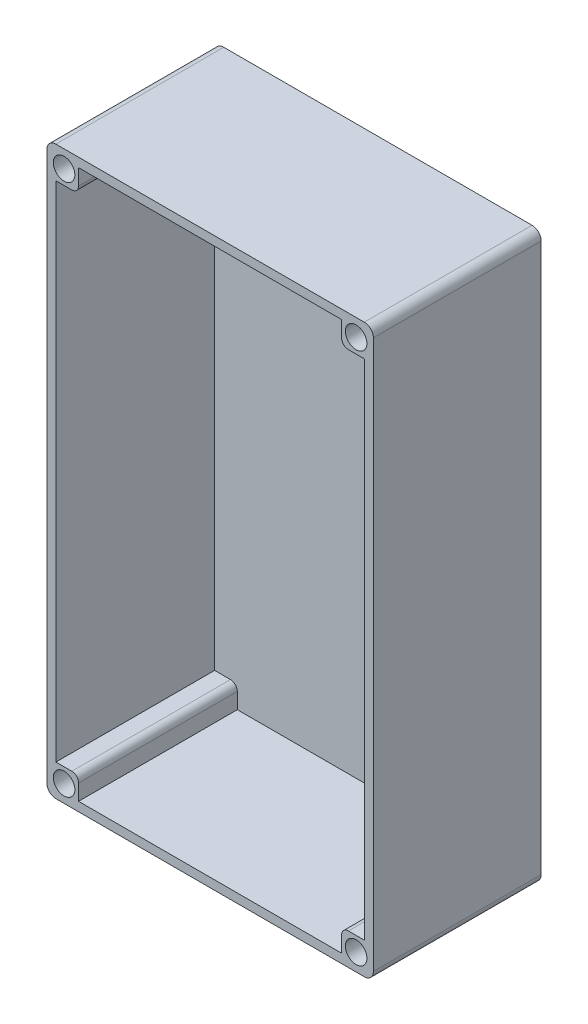
SolidWorks part; units mm, degrees
ref_plane "Front Plane" through (0, 0, 0) normal (0, 0, 1) x (1, 0, 0)
ref_plane "Top Plane" through (0, 0, 0) normal (0, 1, 0) x (1, 0, 0)
ref_plane "Right Plane" through (0, 0, 0) normal (1, 0, 0) x (0, 0, -1)
sketch "Sketch1" plane through (0, 0, 0) normal (0, 0, 1) x (1, 0, 0)
  line L5 (-36, 50) -> (36, 50)
  line L6 (-36, 50) -> (-36, -75)
  line L7 (-36, -75) -> (36, -75)
  line L8 (36, 50) -> (36, -75)
  dimension "D1" = 72
  dimension "D2" = 36
  dimension "D3" = 125
  dimension "D4" = 75
extrude "Boss-Extrude1" add sketch "Sketch1" along normal blind 2
sketch "Sketch2" plane through (0, 0, 2) normal (0, 0, 1) x (1, 0, 0)
  circle A0 centre (-22.86, 38.1) radius 2.3812
  circle A1 centre (-22.86, 20.32) radius 2.3813
  circle A2 centre (22.86, 20.32) radius 2.3812
  circle A3 centre (22.86, 38.1) radius 2.3812
  dimension "D1" = 4.7625
  dimension "D2" = 4.7625
  dimension "D3" = 4.7625
  dimension "D4" = 4.7625
  dimension "D5" = 45.72
  dimension "D6" = 45.72
  dimension "D7" = 17.78
  dimension "D8" = 17.78
  dimension "D9" = 22.86
  dimension "D10" = 20.32
  dimension "D11" = 0
extrude "Boss-Extrude2" [suppressed] add sketch "Sketch2" along normal blind 3.175
sketch "Sketch3" [suppressed] plane through (0, 0, 2) normal (0, 0, 1) x (1, 0, 0)
  line L1 (-25.4, 41.275) -> (25.4, 41.275)
  line L2 (-25.4, 41.275) -> (-25.4, 18.415)
  line L3 (-25.4, 18.415) -> (25.4, 18.415)
  line L4 (25.4, 41.275) -> (25.4, 18.415)
  dimension "D1" = 22.86
  dimension "D2" = 1.905
  dimension "D3" = 2.54
  dimension "D4" = 50.8
fillet "Fillet1" [suppressed] radius 2
sketch "Sketch4" [suppressed] plane through (0, 0, 5.175) normal (0, 0, 1) x (1, 0, 0)
  circle A0 centre (-22.86, 38.1) radius 1.0795
  circle A1 centre (22.86, 38.1) radius 1.0795
  circle A2 centre (22.86, 20.32) radius 1.0795
  circle A3 centre (-22.86, 20.32) radius 1.0795
  dimension "D1" = 2.159
  dimension "D2" = 2.159
  dimension "D3" = 2.159
  dimension "D4" = 2.159
extrude "Cut-Extrude1" [suppressed] cut sketch "Sketch4" against normal through all
sketch "Sketch5" plane through (0, 0, 2) normal (0, 0, 1) x (1, 0, 0)
  line L0 (36, -75) -> (36, 50) construction
  line L1 (-36, 50) -> (36, 50)
  line L2 (-36, 50) -> (-36, 48)
  line L3 (-36, 48) -> (36, 48)
  line L4 (36, 50) -> (36, 48)
  dimension "D1" = 2
extrude "Boss-Extrude3" add sketch "Sketch5" along normal blind 35
sketch "Sketch6" plane through (0, 0, 2) normal (0, 0, 1) x (1, 0, 0)
  line L0 (-36, -75) -> (36, -75) construction
  line L1 (-34, -75) -> (-36, -75)
  line L2 (-34, -75) -> (-34, 50)
  line L3 (-34, 50) -> (-36, 50)
  line L4 (-36, -75) -> (-36, 50)
  dimension "D1" = 2
extrude "Boss-Extrude4" add sketch "Sketch6" along normal blind 35
mirror "Mirror1" [suppressed] about plane through (0, 0, 0) normal (0, 1, 0)
mirror "Mirror2" about plane through (0, 0, 0) normal (1, 0, 0) of "Boss-Extrude4"
mirror "Mirror3" [suppressed] about plane through (0, 0, 0) normal (0, 1, 0)
sketch "Sketch7" plane through (0, 0, 2) normal (0, 0, 1) x (1, 0, 0)
  line L1 (-29, 43) -> (-34, 43)
  line L2 (-29, 43) -> (-29, 48)
  line L3 (-29, 48) -> (-34, 48)
  line L4 (-34, 43) -> (-34, 48)
extrude "Boss-Extrude5" add sketch "Sketch7" along normal up to surface (35 mm away) up to face at (0, -13, 37)
fillet "Fillet2" radius 1.5 1 edges at (-29, 43, 19.5)
sketch "Sketch8" plane through (0, 0, 37) normal (0, 0, 1) x (1, 0, 0)
  line L0 (36, 50) -> (-36, 50) construction
  line L1 (-36, 50) -> (-36, -75) construction
  circle A0 centre (-32.2, 46.2) radius 2.375
  dimension "D1" = 4.75
  dimension "D3" = 3.8
extrude "Cut-Extrude2" cut sketch "Sketch8" against normal through all
mirror "Mirror4" about plane through (0, 0, 0) normal (1, 0, 0) of "Cut-Extrude2", "Boss-Extrude5", "Fillet2"
mirror "Mirror5" [suppressed] about plane through (0, 0, 0) normal (0, 1, 0)
fillet "Fillet3" radius 2 4 edges at (-36, 50, 18.5) (36, 50, 18.5) (-36, -75, 18.5) (36, -75, 18.5)
sketch "Sketch9" plane through (-36, 0, 0) normal (-1, 0, 0) x (0, 0, 1)
  line L0 (0, 48) -> (0, -73) construction
  line L1 (25.0475, 35) -> (14.9525, 35)
  line L2 (26, 34.0475) -> (26, 23.9525)
  line L3 (25.0475, 23) -> (14.9525, 23)
  line L4 (14, 34.0475) -> (14, 23.9525)
  line L5 (0, 50) -> (37, 50) construction
  arc A0 (26, 23.9525) -> (25.0475, 23) centre (25.0475, 23.9525) cw
  arc A1 (25.0475, 35) -> (26, 34.0475) centre (25.0475, 34.0475) cw
  arc A2 (14.9525, 35) -> (14, 34.0475) centre (14.9525, 34.0475) ccw
  arc A3 (14.9525, 23) -> (14, 23.9525) centre (14.9525, 23.9525) cw
  point P10 (26, 23)
  point P13 (26, 35)
  dimension "D5" = 0.9525
  dimension "D1" = 26
  dimension "D2" = 14
  dimension "D3" = 12
  dimension "D4" = 15
extrude "Cut-Extrude3" [suppressed] cut sketch "Sketch9" against normal up to next
sketch "Sketch10" [suppressed] plane through (0, 0, 0) normal (0, 0, -1) x (-1, 0, 0)
  circle A0 centre (22.86, 38.1) radius 1.905
  circle A1 centre (22.86, 20.32) radius 1.905
  dimension "D1" = 3.81
  dimension "D2" = 3.81
extrude "Cut-Extrude4" [suppressed] cut sketch "Sketch10" against normal blind 2.286
mirror "Mirror6" [suppressed] about plane through (0, 0, 0) normal (1, 0, 0)
mirror "Mirror7" [suppressed] about plane through (0, 0, 0) normal (0, 1, 0)
sketch "Sketch11" [suppressed] plane through (-28.575, 0, 0) normal (-1, 0, 0) x (0, 0, 1)
  line L0 (2.286, -20.32) -> (5.175, -20.32) construction
  line L1 (10.7295, -21.72) -> (27.2492, -21.72)
  line L2 (8.7295, -23.72) -> (8.7295, -34.72)
  line L3 (10.7295, -36.72) -> (27.2492, -36.72)
  line L4 (29.2492, -23.72) -> (29.2492, -34.72)
  arc A0 (8.7295, -34.72) -> (10.7295, -36.72) centre (10.7295, -34.72) ccw
  arc A1 (27.2492, -36.72) -> (29.2492, -34.72) centre (27.2492, -34.72) ccw
  arc A2 (27.2492, -21.72) -> (29.2492, -23.72) centre (27.2492, -23.72) cw
  arc A3 (10.7295, -21.72) -> (8.7295, -23.72) centre (10.7295, -23.72) ccw
  point P10 (29.2492, -36.72)
  point P13 (29.2492, -21.72)
  dimension "D3" = 2
  dimension "D1" = 15
  dimension "D2" = 1.4
extrude "Cut-Extrude5" [suppressed] cut sketch "Sketch11" against normal up to next
sketch "Sketch12" plane through (0, 0, 2) normal (0, 0, 1) x (1, 0, 0)
  line L0 (34, -75) -> (34, 43) construction
  line L1 (-34, -75) -> (34, -75)
  line L2 (-34, -75) -> (-34, -73)
  line L3 (-34, -73) -> (34, -73)
  line L4 (34, -75) -> (34, -73)
  dimension "D1" = 2
extrude "Boss-Extrude6" add sketch "Sketch12" along normal up to surface (35 mm away) up to face at (29.825, 46.2, 37)
sketch "Sketch13" plane through (0, 0, 37) normal (0, 0, 1) x (1, 0, 0)
  line L1 (-34, -73) -> (-29, -73)
  line L2 (-34, -73) -> (-34, -68)
  line L3 (-34, -68) -> (-29, -68)
  line L4 (-29, -73) -> (-29, -68)
  dimension "D1" = 5
  dimension "D2" = 5
extrude "Boss-Extrude9" add sketch "Sketch13" against normal up to surface (35 mm away) up to face at (0, 21.0379, 2)
sketch "Sketch14" plane through (0, 0, 37) normal (0, 0, 1) x (1, 0, 0)
  line L0 (-36, 48) -> (-36, -73) construction
  line L1 (-34, -75) -> (34, -75) construction
  circle A0 centre (-32.2, -71.2) radius 2.375
  dimension "D1" = 4.75
  dimension "D3" = 3.8
extrude "Cut-Extrude6" cut sketch "Sketch14" against normal through all
fillet "Fillet4" radius 1.5 1 edges at (-29, -68, 19.5)
mirror "Mirror8" about plane through (0, 0, 0) normal (1, 0, 0) of "Fillet4", "Cut-Extrude6", "Boss-Extrude9"
equation "\"D4@Sketch1\"=75"
equation "\"D2@Sketch2\"=\"D1@Sketch2\""
equation "\"D3@Sketch2\"=\"D2@Sketch2\""
equation "\"D4@Sketch2\"=\"D2@Sketch2\""
equation "\"D9@Sketch2\"=\"D5@Sketch2\"/2"
equation "\"D7@Sketch2\"=\"D8@Sketch2\""
equation "\"D2@Sketch4\"=\"D1@Sketch4\""
equation "\"D3@Sketch4\"=\"D1@Sketch4\""
equation "\"D4@Sketch4\"=\"D3@Sketch4\""
equation "\"D2@Sketch1\"=\"D1@Sketch1\"/2"
equation "\"D2@Sketch8\"=\"D1@Sketch8\"/1.25"
equation "\"D3@Sketch8\"=\"D1@Sketch8\"/1.25"
equation "\"D2@Sketch7\"=\"D1@Sketch7\""
equation "\"D2@Sketch10\"=\"D1@Sketch10\""
equation "\"D2@Sketch14\"=\"D1@Sketch14\"/1.25"
equation "\"D3@Sketch14\"=\"D1@Sketch14\"/1.25"
